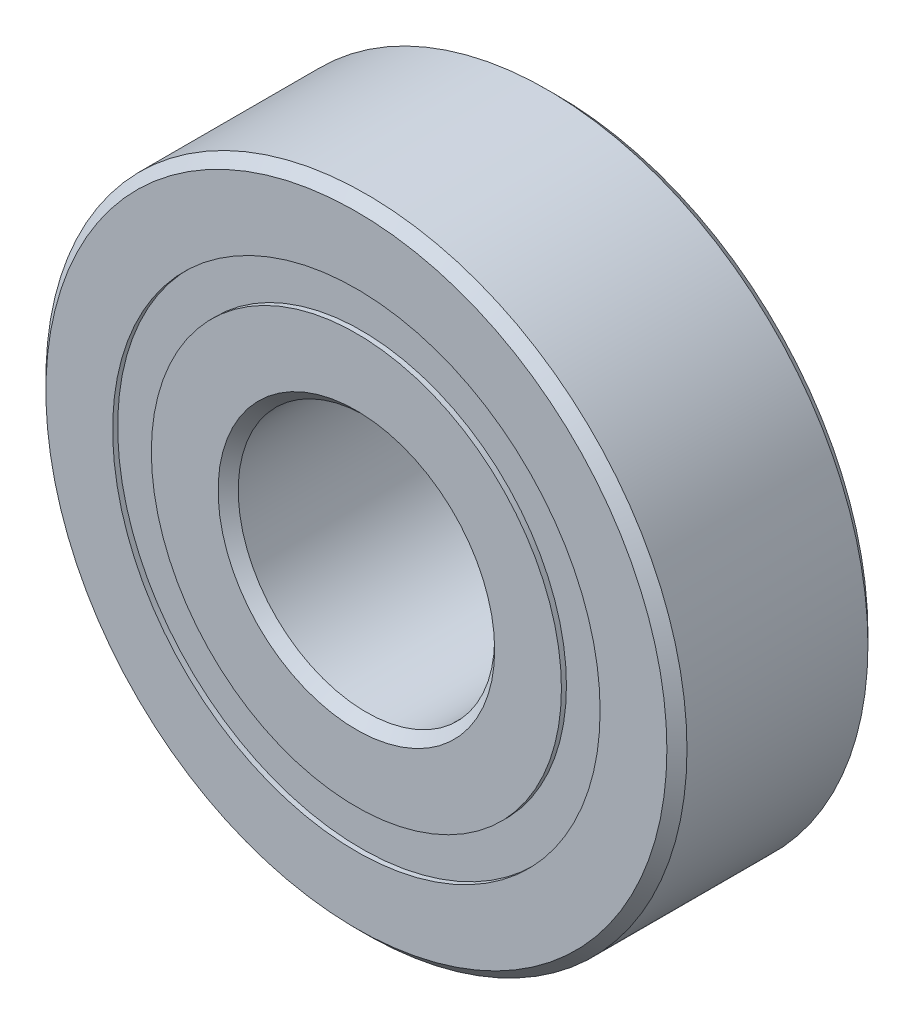
SolidWorks part; units mm, degrees
ref_plane "Front Plane" through (0, 0, 0) normal (0, 0, 1) x (1, 0, 0)
ref_plane "Top Plane" through (0, 0, 0) normal (0, 1, 0) x (1, 0, 0)
ref_plane "Right Plane" through (0, 0, 0) normal (1, 0, 0) x (0, 0, -1)
sketch "Sketch1" plane through (0, 0, 0) normal (1, 0, 0) x (0, 0, -1)
  line L0 (-2.4892, 0) -> (2.4892, 0) construction
  line L1 (0, 7.9375) -> (0, -7.9375) construction
  line L2 (2.2403, 7.9375) -> (-2.2403, 7.9375)
  line L3 (-2.2403, 7.9375) -> (-2.4892, 7.6886)
  line L4 (-2.4892, 7.6886) -> (-2.4892, 6.0352)
  line L5 (-2.4892, 6.0352) -> (-1.1063, 6.0352)
  line L6 (2.4892, 6.0352) -> (1.1063, 6.0352)
  line L7 (2.4892, 7.6886) -> (2.4892, 6.0352)
  line L8 (2.2403, 7.9375) -> (2.4892, 7.6886)
  line L9 (0, 7.9375) -> (0, 5.5563) construction
  line L10 (0, 5.5563) -> (0, 3.175) construction
  arc A0 (-1.1063, 6.0352) -> (1.1063, 6.0352) centre (0, 5.5563) cw
  point P14 (0, 3.175)
  dimension "Width" = 4.9784
  dimension "OD" = 15.875
  dimension "D1" = 45
  dimension "D2" = 0.2489
  dimension "Shaft Dia" = 6.35
  dimension "D3" = 2.2126
  dimension "D4" = 0.479
revolve "Revolve1" add sketch "Sketch1" angle 360 about L0
sketch "Sketch3" plane through (0, 0, 0) normal (1, 0, 0) x (0, 0, -1)
  line L0 (-2.4892, 5.0773) -> (-1.1063, 5.0773)
  line L1 (0, 7.9375) -> (0, -7.9375) construction
  line L2 (-2.4892, 7.6886) -> (-2.4892, 6.0352) construction
  line L3 (-2.4892, 5.0773) -> (-2.4892, 3.4239)
  line L4 (-2.2403, 7.9375) -> (-2.4892, 7.6886) construction
  line L5 (-2.4892, 3.4239) -> (-2.2403, 3.175)
  line L6 (-2.2403, 3.175) -> (2.2403, 3.175)
  line L7 (2.2403, 7.9375) -> (2.2403, -7.9375) construction
  line L8 (2.2403, 3.175) -> (2.4892, 3.4239)
  line L9 (2.4892, -7.6886) -> (2.4892, 7.6886) construction
  line L10 (2.4892, 3.4239) -> (2.4892, 5.0773)
  line L11 (2.4892, 5.0773) -> (1.1063, 5.0773)
  line L13 (2.2403, 7.9375) -> (2.4892, 7.6886) construction
  arc A0 (1.1063, 6.0352) -> (-1.1063, 6.0352) centre (0, 5.5563) ccw construction
  arc A1 (1.1063, 5.0773) -> (-1.1063, 5.0773) centre (0, 5.5562) cw
revolve "Revolve3" add sketch "Sketch3" angle 360 about L0
sketch "Sketch4" plane through (0, 0, 0) normal (1, 0, 0) x (0, 0, -1)
  line L0 (-1.2055, 5.5563) -> (1.2055, 5.5563)
  arc A2 (-1.2055, 5.5563) -> (1.2055, 5.5563) centre (0, 5.5563) cw
  arc A3 (1.1063, 6.0352) -> (-1.1063, 6.0352) centre (0, 5.5563) ccw construction
revolve "Revolve4" add sketch "Sketch4" angle 360 about L0
ref_axis "Axis1" through (0, 0, -2.4892) along (0, 0, 1)
pattern_circular "CirPattern1" count 10 every 36 about axis through (0, 0, -2.4892) along (0, 0, 1) of bodies 104
sketch "Sketch5" plane through (0, 0, 0) normal (1, 0, 0) x (0, 0, -1)
  line L0 (-2.4892, 6.0352) -> (-1.1063, 6.0352) construction
  line L1 (-2.3647, 6.0352) -> (-1.2055, 6.0352)
  line L2 (-2.3647, 6.0352) -> (-2.3647, 5.0773)
  line L3 (-2.3647, 5.0773) -> (-1.2055, 5.0773)
  line L4 (-1.2055, 6.0352) -> (-1.2055, 5.0773)
  line L5 (-2.4892, 5.0773) -> (-1.1063, 5.0773) construction
  line L6 (2.4892, 6.0352) -> (1.1063, 6.0352) construction
  line L7 (2.3647, 6.0352) -> (1.2055, 6.0352)
  line L8 (2.3647, 6.0352) -> (2.3647, 5.0773)
  line L9 (2.3647, 5.0773) -> (1.2055, 5.0773)
  line L10 (1.2055, 6.0352) -> (1.2055, 5.0773)
  line L11 (2.4892, 5.0773) -> (1.1063, 5.0773) construction
  line L12 (-2.2403, 7.9375) -> (-2.4892, 7.6886) construction
  point P18 (-2.3647, 7.813)
revolve "Revolve5" add sketch "Sketch5" angle 360 about L0
equation "\"D2@Sketch1\" = \"Width@Sketch1\"*.05"
equation "\"D3@Sketch1\" = \"Width@Sketch1\"/2.25"
equation "\"D4@Sketch1\" = (((\"OD@Sketch1\"-\"Width@Sketch1\")/2)/3.25)/3.5"
equation "\"D2@CirPattern1\" = 360/\"Balls@CirPattern1\""
